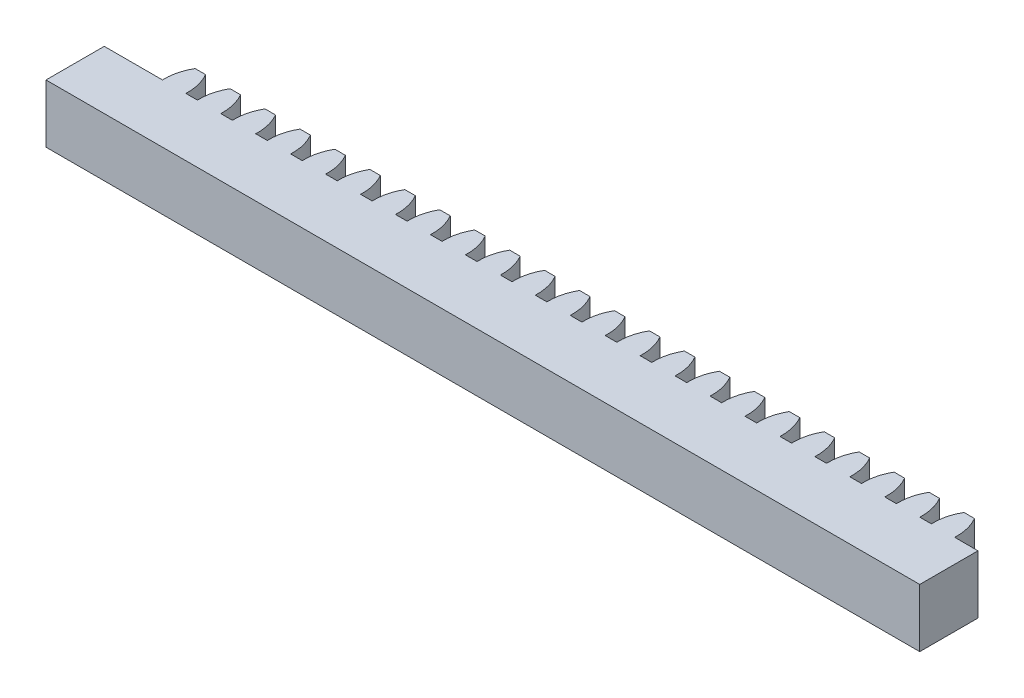
SolidWorks part; units mm, degrees
ref_plane "Front Plane" through (0, 0, 0) normal (0, 0, 1) x (1, 0, 0)
ref_plane "Top Plane" through (0, 0, 0) normal (0, 1, 0) x (1, 0, 0)
ref_plane "Right Plane" through (0, 0, 0) normal (1, 0, 0) x (0, 0, -1)
sketch "Sketch2" plane through (0, 0, 0) normal (0, 1, 0) x (1, 0, 0)
  line L0 (-32.7528, 0) -> (42.2472, 0)
  line L1 (42.2472, 0) -> (42.2472, 5)
  line L2 (42.2472, 5) -> (-32.7528, 5)
  line L3 (-32.7528, 5) -> (-32.7528, 0)
  line L4 (-27.7528, 5) -> (-27.7528, 8.2168) construction
  line L5 (37.2472, 5) -> (37.2472, 8.2384) construction
  line L6 (-27.2028, 7.25) -> (-26.3028, 7.25)
  line L7 (-26.7528, 7.25) -> (-26.7528, 4.3153) construction
  arc A0 (-27.7528, 5) -> (-27.2028, 7.25) centre (-23.6394, 5.1867) cw
  arc A1 (-25.7528, 5) -> (-26.3028, 7.25) centre (-29.8662, 5.1867) ccw
  point P11 (-27.2051, 7.3418)
  dimension "D1" = 75
  dimension "D2" = 5
  dimension "D3" = 5
  dimension "D4" = 5
  dimension "D5" = 1
  dimension "D6" = 0.45
  dimension "D7" = 2.25
extrude "Boss-Extrude1" add sketch "Sketch2" along normal blind 5 contours L2 L3 L0 L1 region at (4.7472, 0, -2.5)
extrude "Boss-Extrude2" add sketch "Sketch2<3>" along normal blind 5 contours L2 A1 L6 A0 region at (-26.7528, 0, -6.0043)
sketch "Sketch2<3>" plane through (0, 0, 0) normal (0, 1, 0) x (1, 0, 0) same geometry as "Sketch2"
pattern_linear "LPattern1" count 23 spacing 3 along (1, 0, 0) of "Boss-Extrude2"
